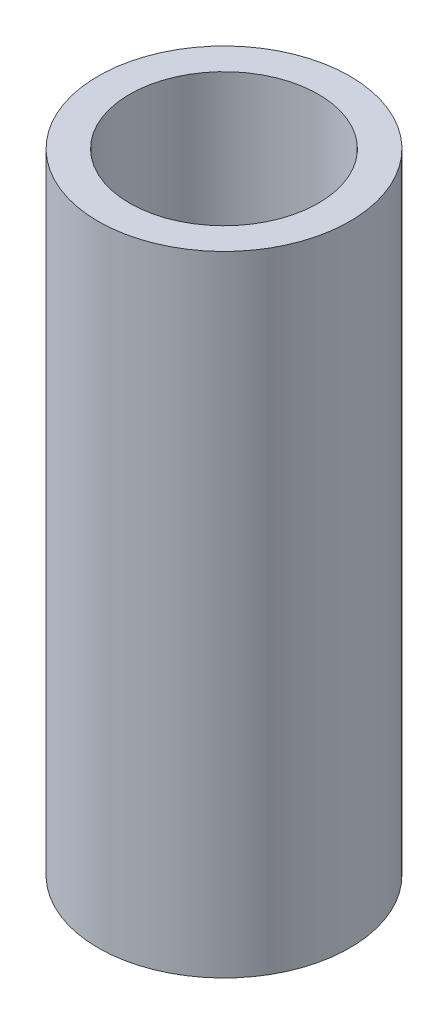
SolidWorks part; units mm, degrees
ref_plane "Спереди" through (0, 0, 0) normal (0, 0, 1) x (1, 0, 0)
ref_plane "Сверху" through (0, 0, 0) normal (0, 1, 0) x (1, 0, 0)
ref_plane "Справа" through (0, 0, 0) normal (1, 0, 0) x (0, 0, -1)
sketch "Эскиз1" plane through (0, 0, 0) normal (0, 1, 0) x (1, 0, 0)
  circle A0 centre (0, 0) radius 3
  circle A1 centre (0, 0) radius 4
  dimension "D1" = 6
  dimension "D2" = 8
extrude "Бобышка-Вытянуть1" add sketch "Эскиз1" along normal blind 20
